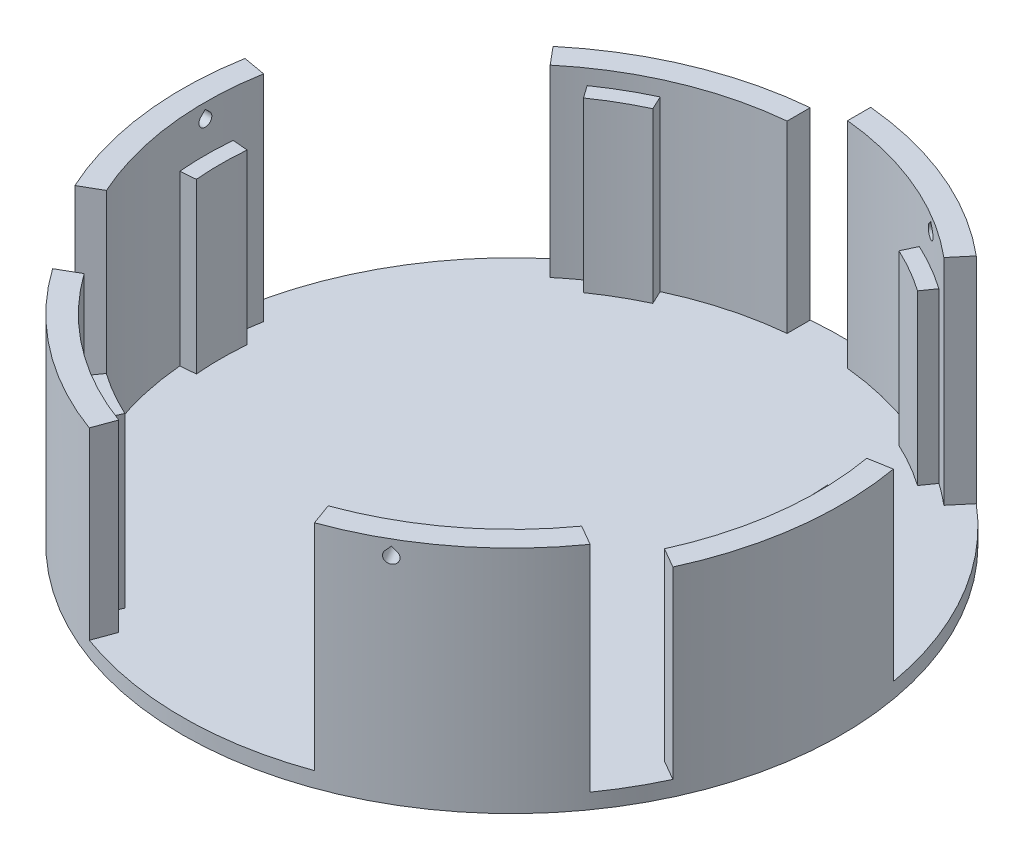
SolidWorks part; units mm, degrees
ref_plane "Front Plane" through (0, 0, 0) normal (0, 0, 1) x (1, 0, 0)
ref_plane "Top Plane" through (0, 0, 0) normal (0, 1, 0) x (1, 0, 0)
ref_plane "Right Plane" through (0, 0, 0) normal (1, 0, 0) x (0, 0, -1)
sketch "Sketch1" plane through (0, 0, 0) normal (0, 1, 0) x (1, 0, 0)
  circle A0 centre (0, 0) radius 107.5
  dimension "D1" = 215
extrude "Boss-Extrude1" add sketch "Sketch1" along normal blind 5
sketch "Sketch2" plane through (0, 5, 0) normal (0, 1, 0) x (1, 0, 0)
  line L0 (0, 0) -> (0, 107.5) construction
  line L3 (-9.7561, 99.523) -> (-9.7561, 107.0564)
  line L5 (10, 99.4987) -> (10, 107.0339)
  line L6 (91.0675, -41.3124) -> (97.5916, -45.0792)
  line L8 (81.1684, -58.4096) -> (87.6941, -62.1772)
  line L10 (-81.3114, -58.2105) -> (-87.8355, -61.9772)
  line L12 (-91.1684, -41.0891) -> (-97.6941, -44.8567)
  arc A0 (-9.7561, 107.0564) -> (-97.6941, -44.8567) centre (0, 0) ccw
  arc A1 (-9.7561, 99.523) -> (-91.1684, -41.0891) centre (0, 0) ccw
  arc A2 (-81.3114, -58.2105) -> (81.1684, -58.4096) centre (0, 0) ccw
  arc A3 (-87.8355, -61.9772) -> (87.6941, -62.1772) centre (0, 0) ccw
  arc A4 (91.0675, -41.3124) -> (10, 99.4987) centre (0, 0) ccw
  arc A5 (97.5916, -45.0792) -> (10, 107.0339) centre (0, 0) ccw
  point P20 (0, 0)
  dimension "D1" = 200
  dimension "D2" = 215
  dimension "D4" = 10
  dimension "D7" = 3
extrude "Boss-Extrude2" add sketch "Sketch2" along normal blind 70
ref_plane "Plane1" through (-107.5, 0, 0) normal (-1, 0, 0) x (0, 0, 1)
ref_plane "Plane2" through (53.75, 0, 93.0977) normal (0.5, 0, 0.866) x (0.866, 0, -0.5)
ref_plane "Plane3" through (53.75, 0, -93.0977) normal (0.5, 0, -0.866) x (-0.866, 0, -0.5)
sketch "Sketch4" plane through (-107.5, 0, 0) normal (-1, 0, 0) x (0, 0, 1)
  line L0 (44.8567, 75) -> (-107.0564, 75) construction
  line L1 (-1.4849, 71.4849) -> (0, 72.9698)
  line L2 (0, 72.9698) -> (1.4849, 71.4849)
  arc A0 (-1.4849, 71.4849) -> (1.4849, 71.4849) centre (0, 70) ccw
  dimension "D1" = 4.2
  dimension "D2" = 5
  dimension "D3" = 90
extrude "Cut-Extrude2" cut sketch "Sketch4" against normal blind 10 and the other way blind 10
ref_plane "Plane4" through (0, 5, 0) normal (0, 1, 0) x (1, 0, 0)
sketch "Sketch6" plane through (0, 5, 0) normal (0, 1, 0) x (1, 0, 0)
  line L0 (0, 0) -> (100, 0) construction
  line L1 (94.6385, 8.2798) -> (99.6195, 8.7156)
  line L2 (94.6385, -8.2798) -> (99.6195, -8.7156)
  line L7 (54.4898, -77.8194) -> (57.3576, -81.9152)
  line L8 (40.1487, -86.0992) -> (42.2618, -90.6308)
  line L9 (-40.1487, -86.0992) -> (-42.2618, -90.6308)
  line L10 (-54.4898, -77.8194) -> (-57.3576, -81.9152)
  line L11 (-94.6385, -8.2798) -> (-99.6195, -8.7156)
  line L12 (-94.6385, 8.2798) -> (-99.6195, 8.7156)
  line L13 (-54.4898, 77.8194) -> (-57.3576, 81.9152)
  line L14 (-40.1487, 86.0992) -> (-42.2618, 90.6308)
  line L15 (40.1487, 86.0992) -> (42.2618, 90.6308)
  line L16 (54.4898, 77.8194) -> (57.3576, 81.9152)
  arc A1 (91.0675, -41.3124) -> (10, 99.4987) centre (0, 0) ccw construction
  arc A2 (91.0675, -41.3124) -> (10, 99.4987) centre (0, 0) ccw construction
  arc A3 (99.6195, -8.7156) -> (99.6195, 8.7156) centre (0, 0) ccw
  arc A4 (94.6385, -8.2798) -> (94.6385, 8.2798) centre (0, 0) ccw
  arc A9 (42.2618, -90.6308) -> (57.3576, -81.9152) centre (0, 0) ccw
  arc A10 (40.1487, -86.0992) -> (54.4898, -77.8194) centre (0, 0) ccw
  arc A11 (-57.3576, -81.9152) -> (-42.2618, -90.6308) centre (0, 0) ccw
  arc A12 (-54.4898, -77.8194) -> (-40.1487, -86.0992) centre (0, 0) ccw
  arc A13 (-99.6195, 8.7156) -> (-99.6195, -8.7156) centre (0, 0) ccw
  arc A14 (-94.6385, 8.2798) -> (-94.6385, -8.2798) centre (0, 0) ccw
  arc A15 (-42.2618, 90.6308) -> (-57.3576, 81.9152) centre (0, 0) ccw
  arc A16 (-40.1487, 86.0992) -> (-54.4898, 77.8194) centre (0, 0) ccw
  arc A17 (57.3576, 81.9152) -> (42.2618, 90.6308) centre (0, 0) ccw
  arc A18 (54.4898, 77.8194) -> (40.1487, 86.0992) centre (0, 0) ccw
  point P24 (0, 0)
  point P38 (0, 0)
  dimension "D1" = 6
  dimension "D2" = 190
  dimension "D3" = 5
  dimension "D4" = 5
extrude "Boss-Extrude4" add sketch "Sketch6" along normal blind 55
sketch "Sketch7" plane through (53.75, 0, 93.0977) normal (0.5, 0, 0.866) x (0.866, 0, -0.5)
  line L0 (44.8567, 75) -> (-107.0564, 75) construction
  line L1 (0, 72.9698) -> (-1.4849, 71.4849)
  line L2 (0, 72.9698) -> (1.4849, 71.4849)
  arc A0 (-1.4849, 71.4849) -> (1.4849, 71.4849) centre (0, 70) ccw
  dimension "D1" = 4.2
  dimension "D2" = 5
  dimension "D3" = 90
extrude "Cut-Extrude3" cut sketch "Sketch7" against normal blind 10 and the other way blind 10
sketch "Sketch8" plane through (53.75, 0, -93.0977) normal (0.5, 0, -0.866) x (-0.866, 0, -0.5)
  line L0 (44.8567, 75) -> (-107.0564, 75) construction
  line L1 (-1.4849, 71.4849) -> (0, 72.9698)
  line L2 (0, 72.9698) -> (1.4849, 71.4849)
  arc A0 (-1.4849, 71.4849) -> (1.4849, 71.4849) centre (0, 70) ccw
  dimension "D1" = 4.2
  dimension "D2" = 5
  dimension "D3" = 90
extrude "Cut-Extrude4" cut sketch "Sketch8" against normal blind 10 and the other way blind 10
sketch "Sketch10" plane through (0, 5, 0) normal (0, 1, 0) x (1, 0, 0)
  line L0 (-34.309, -93.9302) -> (-36.8822, -100.975)
  line L1 (34.0949, -94.0082) -> (36.6521, -101.0588)
  line L2 (0, 0) -> (-0.1225, -107.4999) construction
  line L3 (-64.1914, 76.6776) -> (-69.0058, 82.4284)
  line L4 (-98.4609, 17.477) -> (-105.8455, 18.7878)
  line L5 (98.5005, 17.2526) -> (105.888, 18.5466)
  line L6 (64.366, 76.5312) -> (69.1934, 82.271)
  arc A0 (-87.8355, -61.9772) -> (87.6941, -62.1772) centre (0, 0) ccw construction
  arc A1 (-34.309, -93.9302) -> (34.0949, -94.0082) centre (0, 0) ccw
  arc A2 (-36.8822, -100.975) -> (36.6521, -101.0588) centre (0, 0) ccw
  arc A3 (-64.1914, 76.6776) -> (-98.4609, 17.477) centre (0, 0) ccw
  arc A4 (-69.0058, 82.4284) -> (-105.8455, 18.7878) centre (0, 0) ccw
  arc A5 (98.5005, 17.2526) -> (64.366, 76.5312) centre (0, 0) ccw
  arc A6 (105.888, 18.5466) -> (69.1934, 82.271) centre (0, 0) ccw
  point P20 (0, 0)
  dimension "D3" = 200
  dimension "D4" = 3
  dimension "D1" = 20
  dimension "D2" = 20
extrude "Cut-Extrude5" cut sketch "Sketch10" along normal blind 80
sketch "Sketch11" plane through (0, 75, 0) normal (0, 1, 0) x (1, 0, 0)
  line L0 (-64.1914, 76.6776) -> (-69.0058, 82.4284)
  line L1 (-9.0754, 99.5873) -> (-9.7561, 107.0564)
  line L2 (98.5005, 17.2526) -> (105.888, 18.5466)
  line L3 (90.7829, -41.9341) -> (97.5916, -45.0792)
  line L4 (-34.309, -93.9302) -> (-36.8822, -100.975)
  line L5 (-81.7074, -57.6532) -> (-87.8355, -61.9772)
  arc A0 (-9.7561, 107.0564) -> (-69.0058, 82.4284) centre (0, 0) ccw
  arc A1 (-9.0754, 99.5873) -> (-64.1914, 76.6776) centre (0, 0) ccw
  arc A2 (97.5916, -45.0792) -> (105.888, 18.5466) centre (0, 0) ccw
  arc A3 (90.7829, -41.9341) -> (98.5005, 17.2526) centre (0, 0) ccw
  arc A4 (-87.8355, -61.9772) -> (-36.8822, -100.975) centre (0, 0) ccw
  arc A5 (-81.7074, -57.6532) -> (-34.309, -93.9302) centre (0, 0) ccw
  point P18 (0, 0)
  dimension "D1" = 3
extrude "Cut-Extrude6" cut sketch "Sketch11" against normal blind 10
